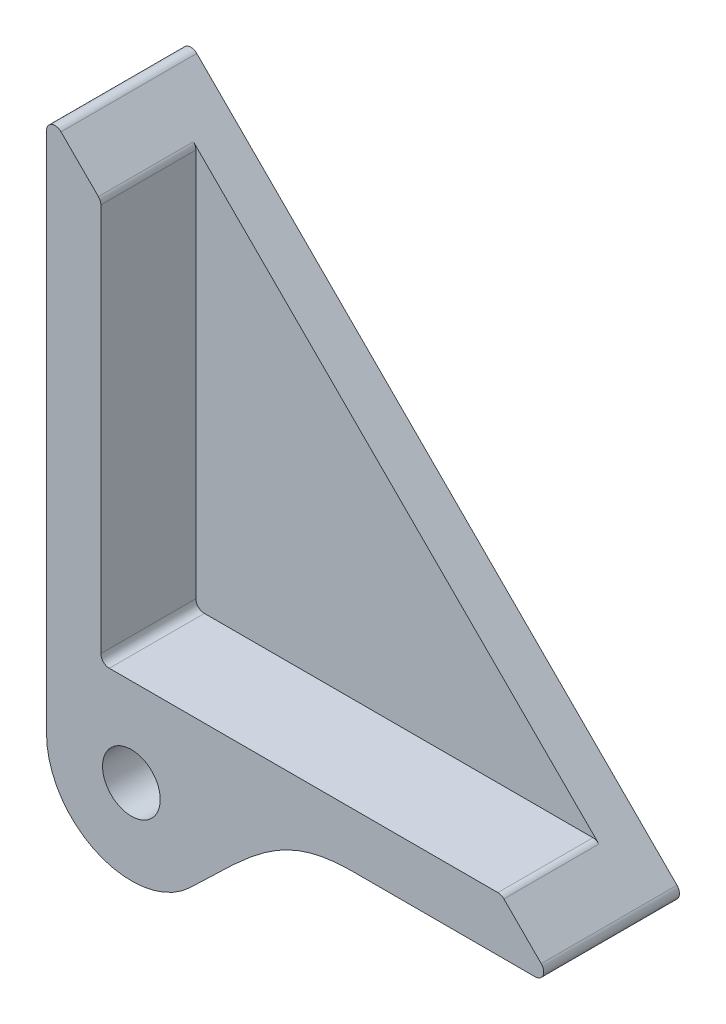
SolidWorks part; units mm, degrees
ref_plane "Front Plane" through (0, 0, 0) normal (0, 0, 1) x (1, 0, 0)
ref_plane "Top Plane" through (0, 0, 0) normal (0, 1, 0) x (1, 0, 0)
ref_plane "Right Plane" through (0, 0, 0) normal (1, 0, 0) x (0, 0, -1)
sketch "Sketch1" plane through (0, 0, 0) normal (0, 0, 1) x (1, 0, 0)
  line L0 (0, 0) -> (0, 30)
  line L1 (0, 30) -> (30, 0)
  line L2 (30, 0) -> (0, 0) construction
  line L3 (0, 0) -> (5, -2) construction
  line L4 (5, -2) -> (10, 0) construction
  line L5 (0, 0) -> (0, -2)
  line L6 (18, 0) -> (30, 0)
  circle A0 centre (5, -2) radius 1.7
  circle A1 centre (5, -2) radius 5 construction
  arc A2 (0, -2) -> (8.4575, -5.6119) centre (5, -2) ccw
  spline S0 degree 3 poles (18, 0) (13.8512, 0) (12.0908, -2.1339) (8.4575, -5.6119) knots 0 0 0 0 1 1 1 1
  point P13 (12.0909, 0.982)
  dimension "D4" = 3.4
  dimension "D5" = 12
  dimension "D6" = 10
  dimension "D1" = 30
  dimension "D2" = 30
  dimension "D3" = 2
extrude "Boss-Extrude1" add sketch "Sketch1" along normal blind 8
sketch "Sketch2" plane through (0, 0, 8) normal (0, 0, 1) x (1, 0, 0)
  line L0 (3.2, 26.8) -> (3.2, 3.2)
  line L1 (3.2, 3.2) -> (26.8, 3.2)
  line L2 (26.8, 3.2) -> (3.2, 26.8)
  line L3 (30, 0) -> (0, 30) construction
  line L4 (0, 30) -> (0, -2) construction
  line L5 (18, 0) -> (30, 0) construction
  dimension "D1" = 3.2
  dimension "D2" = 3.2
extrude "Cut-Extrude1" cut sketch "Sketch2" against normal blind 5.6
fillet "Fillet1" radius 0.5 5 edges at (3.2, 3.2, 5.2) (3.2, 26.8, 5.2) (26.8, 3.2, 5.2) (30, 0, 4) (0, 30, 4)
sketch "Sketch5" plane through (0, 0, 0) normal (0, 0, -1) x (-1, 0, 0)
  circle A0 centre (-5, -2) radius 3.7
  dimension "D1" = 7.4
extrude "Cut-Extrude2" cut sketch "Sketch5" against normal blind 1
chamfer "Chamfer1" distance 2 angle 45 1 edges at (3.3, -2, 1)
ref_plane "Plane2" through (0, 0, 3) normal (0, 0, 1) x (1, 0, 0)
sketch "Sketch6" plane through (0, 0, 3) normal (0, 0, 1) x (1, 0, 0)
  circle A0 centre (5, -2) radius 1.7 construction
  circle A1 centre (5, -2) radius 1.7
extrude "Boss-Extrude2" add sketch "Sketch6" along normal blind 0.4
ref_plane "Plane3" through (0, 0, 1) normal (0, 0, 1) x (1, 0, 0)
sketch "Sketch7" plane through (0, 0, 1) normal (0, 0, 1) x (1, 0, 0)
  circle A0 centre (5, -2) radius 3.7 construction
  circle A1 centre (5, -2) radius 3.7
extrude "Boss-Extrude3" add sketch "Sketch7" against normal blind 0.4
